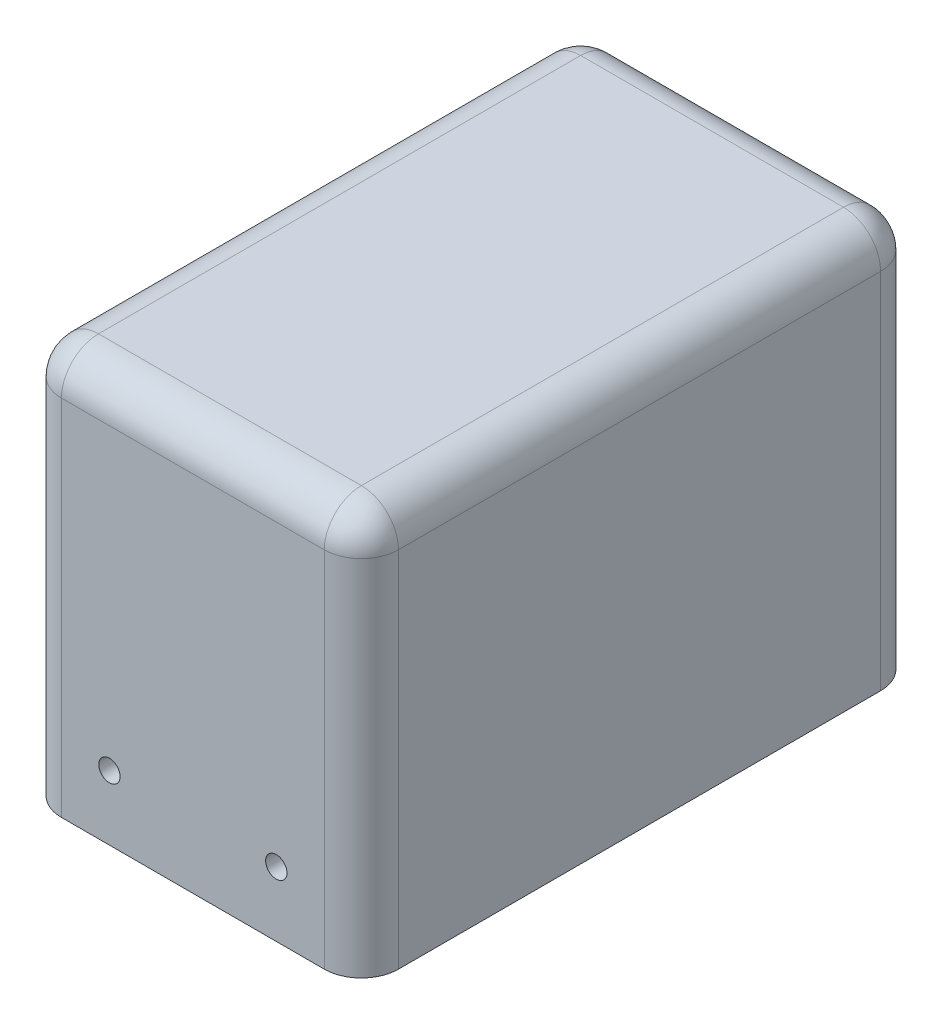
SolidWorks part; units mm, degrees
ref_plane "Front Plane" through (0, 0, 0) normal (0, 0, 1) x (1, 0, 0)
ref_plane "Top Plane" through (0, 0, 0) normal (0, 1, 0) x (1, 0, 0)
ref_plane "Right Plane" through (0, 0, 0) normal (1, 0, 0) x (0, 0, -1)
sketch "Sketch1" plane through (0, 0, 0) normal (0, 1, 0) x (1, 0, 0)
  line L1 (-18.175, 30) -> (18.175, 30)
  line L2 (-18.175, 30) -> (-18.175, -30)
  line L3 (-18.175, -30) -> (18.175, -30)
  line L4 (18.175, 30) -> (18.175, -30)
  line L5 (-18.175, 30) -> (18.175, -30) construction
  line L6 (-18.175, -30) -> (18.175, 30) construction
  line L7 (-15, 26.825) -> (15, 26.825)
  line L8 (-15, 26.825) -> (-15, -26.825)
  line L9 (-15, -26.825) -> (15, -26.825)
  line L10 (15, 26.825) -> (15, -26.825)
  line L11 (-15, 26.825) -> (15, -26.825) construction
  line L12 (-15, -26.825) -> (15, 26.825) construction
  point P0 (0, 0)
  point P6 (0, 0)
  dimension "D1" = 3.175
  dimension "D2" = 3.175
  dimension "D3" = 30
  dimension "D4" = 60
extrude "Boss-Extrude1" add sketch "Sketch1" along normal blind 40
sketch "Sketch2" plane through (0, 40, 0) normal (0, 1, 0) x (1, 0, 0)
  line L1 (-18.175, -30) -> (18.175, -30)
  line L2 (-18.175, -30) -> (-18.175, 30)
  line L3 (-18.175, 30) -> (18.175, 30)
  line L4 (18.175, -30) -> (18.175, 30)
extrude "Boss-Extrude2" add sketch "Sketch2" along normal blind 3.175
fillet "Fillet1" radius 4 8 edges at (-18.175, 43.175, 0) (-18.175, 21.5875, -30) (0, 43.175, -30) (18.175, 21.5875, -30) (18.175, 43.175, 0) (0, 43.175, 30) (18.175, 21.5875, 30) (-18.175, 21.5875, 30)
sketch "Sketch3" plane through (0, 0, 30) normal (0, 0, 1) x (1, 0, 0)
  line L0 (0, 0) -> (0, 39.175) construction
  line L1 (-14.175, 0) -> (14.175, 0) construction
  line L2 (14.175, 39.175) -> (-14.175, 39.175) construction
  circle A0 centre (-9, 6.97) radius 1.15
  circle A1 centre (9, 6.97) radius 1.15
  dimension "D1" = 2.3
  dimension "D2" = 9
  dimension "D3" = 6.97
extrude "Cut-Extrude1" cut sketch "Sketch3" against normal up to surface (3.175 mm away) up to face at (0, 20, 26.825)
sketch "Sketch4" plane through (0, 0, 0) normal (0, -1, 0) x (1, 0, 0)
  line L0 (0, 30) -> (0, -30) construction
  line L1 (-14.175, 30) -> (14.175, 30) construction
  line L2 (14.175, -30) -> (-14.175, -30) construction
  line L3 (-18.175, 0) -> (18.175, 0) construction
  line L4 (-18.175, -26) -> (-18.175, 26) construction
  line L5 (18.175, 26) -> (18.175, -26) construction
  line L6 (-13.175, -17.225) -> (-15, -17.225)
  line L7 (-15, -26.825) -> (-15, 26.825) construction
  line L8 (-13.175, -24.425) -> (-15, -24.425)
  line L9 (-15, -17.225) -> (-15, -24.425)
  line L10 (13.175, -24.425) -> (15, -24.425)
  line L11 (15, -17.225) -> (15, -24.425)
  line L12 (13.175, -17.225) -> (15, -17.225)
  line L13 (15, -26.825) -> (-15, -26.825) construction
  arc A0 (-13.175, -24.425) -> (-13.175, -17.225) centre (-13.175, -20.825) ccw
  arc A1 (13.175, -24.425) -> (13.175, -17.225) centre (13.175, -20.825) cw
  point P24 (0, 0)
  dimension "D1" = 7.2
  dimension "D2" = 5
  dimension "D3" = 6
extrude "Boss-Extrude3" add sketch "Sketch4" against normal blind 3.5
sketch "Sketch5" plane through (0, 0, 0) normal (0, -1, 0) x (1, 0, 0)
  line L0 (0, 30) -> (0, -30) construction
  line L1 (-14.175, 30) -> (14.175, 30) construction
  line L2 (14.175, -30) -> (-14.175, -30) construction
  circle A0 centre (-13.175, -20.825) radius 3.05
  circle A1 centre (13.175, -20.825) radius 3.05
  dimension "D1" = 6.1
extrude "Cut-Extrude2" cut sketch "Sketch5" against normal blind 2.7
